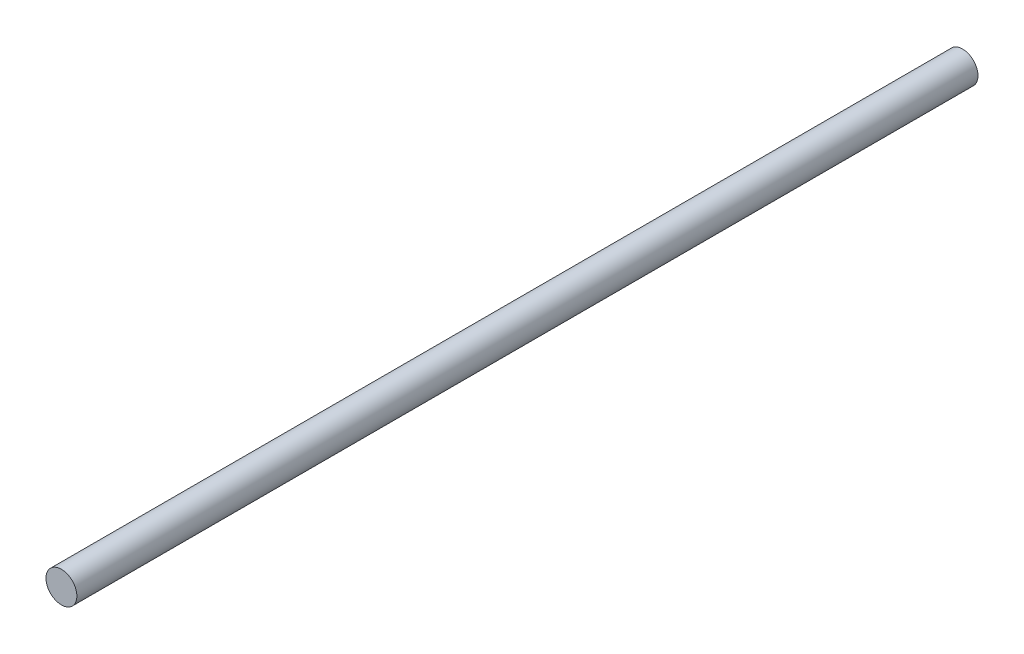
SolidWorks part; units mm, degrees
ref_plane "Ebene vorne" through (0, 0, 0) normal (0, 0, 1) x (1, 0, 0)
ref_plane "Ebene oben" through (0, 0, 0) normal (0, 1, 0) x (1, 0, 0)
ref_plane "Ebene rechts" through (0, 0, 0) normal (1, 0, 0) x (0, 0, -1)
sketch "Skizze1" plane through (0, 0, 0) normal (0, 0, 1) x (1, 0, 0)
  circle A0 centre (0, 0) radius 6
  dimension "D1" = 12
extrude "Aufsatz-Linear austragen1" add sketch "Skizze1" along normal blind 350
ref_point "Punkt1"
